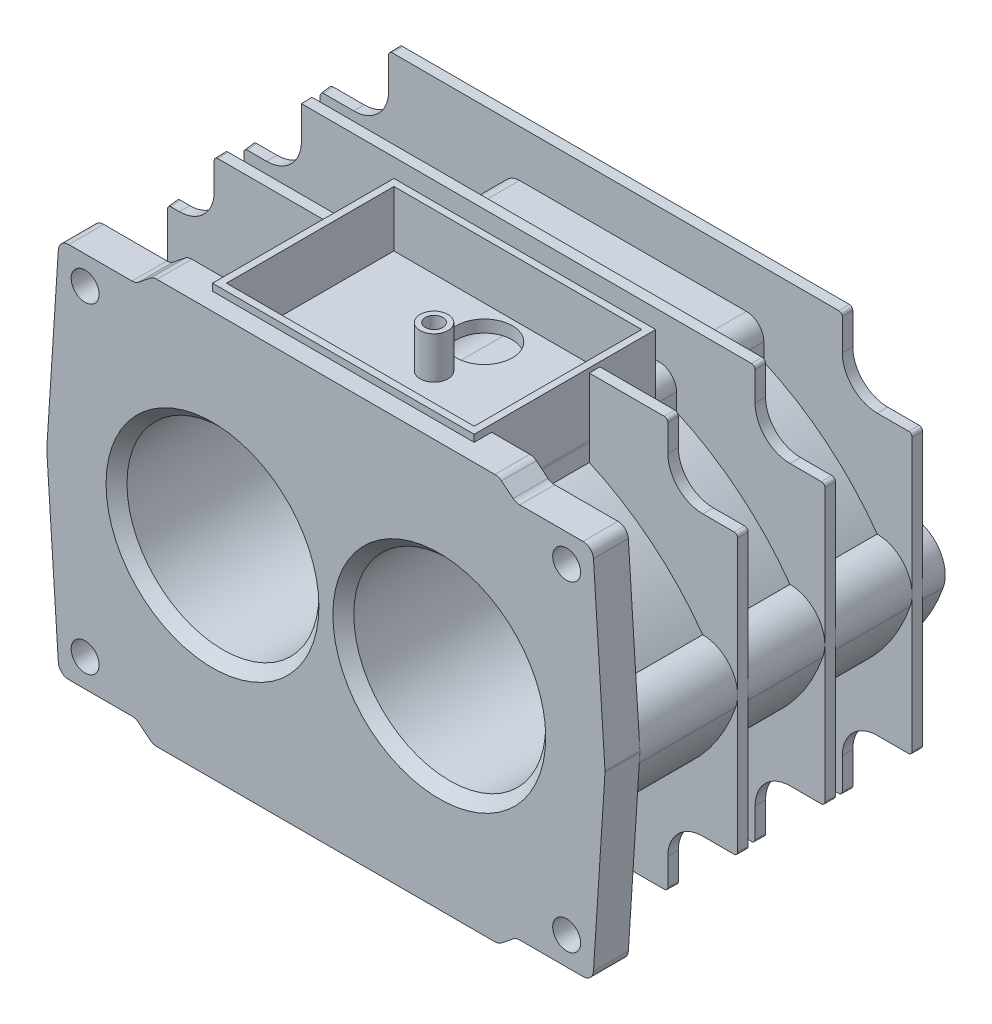
SolidWorks part; units mm, degrees
material "Ghisa grigia"
ref_plane "Piano frontale" through (0, 0, 0) normal (0, 0, 1) x (1, 0, 0)
ref_plane "Piano superiore" through (0, 0, 0) normal (0, 1, 0) x (1, 0, 0)
ref_plane "Piano destro" through (0, 0, 0) normal (1, 0, 0) x (0, 0, -1)
other "Centro di massa"
sketch "Schizzo1" plane through (0, 0, 0) normal (0, 0, 1) x (1, 0, 0)
  line L0 (-80, 0) -> (80, 0) construction
  line L1 (-76.5, 58) -> (76.5, 58) construction
  line L2 (-76.5, 58) -> (-76.5, -58) construction
  line L3 (-48.4477, -58) -> (48.4477, -58)
  line L4 (76.5, 58) -> (76.5, -58) construction
  line L5 (-76.5, 58) -> (76.5, -58) construction
  line L6 (-76.5, -58) -> (76.5, 58) construction
  line L7 (-76.5, -58) -> (76.5, -58) construction
  line L9 (79.9874, -0.194) -> (76.6819, -51.194)
  line L10 (76.6819, 51.194) -> (79.9874, 0.194)
  line L11 (48.4477, 58) -> (-48.4477, 58)
  line L12 (73.6881, -54) -> (55.5523, -54)
  line L13 (-69, 46) -> (69, 46) construction
  line L14 (-69, 46) -> (-69, -46) construction
  line L15 (-69, -46) -> (69, -46) construction
  line L16 (69, 46) -> (69, -46) construction
  line L17 (-69, 46) -> (69, -46) construction
  line L18 (-69, -46) -> (69, 46) construction
  line L19 (73.6881, 54) -> (55.5523, 54)
  line L20 (53.6783, 54.6574) -> (50.3217, 57.3426)
  line L21 (53.6783, -54.6574) -> (50.3217, -57.3426)
  line L22 (0, 72.4767) -> (0, -50.0988) construction
  line L23 (-53.6783, -54.6574) -> (-50.3217, -57.3426)
  line L24 (-73.6881, -54) -> (-55.5523, -54)
  line L25 (-79.9874, -0.194) -> (-76.6819, -51.194)
  line L26 (-76.6819, 51.194) -> (-79.9874, 0.194)
  line L27 (-73.6881, 54) -> (-55.5523, 54)
  line L28 (-53.6783, 54.6574) -> (-50.3217, 57.3426)
  circle A0 centre (-32.5, 0) radius 27.5
  circle A1 centre (32.5, 0) radius 27.5
  circle A2 centre (-69, 46) radius 4
  circle A3 centre (-69, -46) radius 4
  circle A4 centre (69, -46) radius 4
  circle A5 centre (69, 46) radius 4
  arc A6 (-79.9874, -0.194) -> (-79.9874, 0.194) centre (-76.9937, 0) cw
  arc A7 (-73.6881, -54) -> (-76.6819, -51.194) centre (-73.6881, -51) cw
  arc A8 (-53.6783, -54.6574) -> (-55.5523, -54) centre (-55.5523, -57) ccw
  arc A9 (-50.3217, -57.3426) -> (-48.4477, -58) centre (-48.4477, -55) ccw
  arc A10 (50.3217, -57.3426) -> (48.4477, -58) centre (48.4477, -55) cw
  arc A11 (53.6783, -54.6574) -> (55.5523, -54) centre (55.5523, -57) cw
  arc A12 (76.6819, -51.194) -> (73.6881, -54) centre (73.6881, -51) cw
  arc A13 (79.9874, 0.194) -> (79.9874, -0.194) centre (76.9937, 0) cw
  arc A14 (76.6819, 51.194) -> (73.6881, 54) centre (73.6881, 51) ccw
  arc A15 (53.6783, 54.6574) -> (55.5523, 54) centre (55.5523, 57) ccw
  arc A16 (50.3217, 57.3426) -> (48.4477, 58) centre (48.4477, 55) ccw
  arc A17 (-50.3217, 57.3426) -> (-48.4477, 58) centre (-48.4477, 55) cw
  arc A18 (-53.6783, 54.6574) -> (-55.5523, 54) centre (-55.5523, 57) cw
  arc A19 (-73.6881, 54) -> (-76.6819, 51.194) centre (-73.6881, 51) ccw
  point P0 (0, 0)
  point P8 (-32.5, 0)
  point P9 (32.5, 0)
  point P14 (0, 0)
  point P42 (-76.5, -54)
  point P45 (-54.5, -54)
  point P48 (-49.5, -58)
  point P51 (49.5, -58)
  point P54 (54.5, -54)
  point P57 (76.5, -54)
  point P63 (76.5, 54)
  point P66 (54.5, 54)
  point P69 (49.5, 58)
  point P72 (-49.5, 58)
  point P75 (-54.5, 54)
  point P78 (-76.5, 54)
  dimension "D5" = 55
  dimension "D6" = 55
  dimension "D11" = 8
  dimension "D12" = 8
  dimension "D13" = 8
  dimension "D14" = 8
  dimension "D7" = 3
  dimension "D1" = 153
  dimension "D2" = 116
  dimension "D3" = 44
  dimension "D4" = 44
  dimension "D8" = 80
  dimension "D9" = 138
  dimension "D10" = 92
  dimension "D15" = 54
  dimension "D16" = 54
  dimension "D17" = 22
  dimension "D18" = 22
  dimension "D19" = 5
  dimension "D20" = 5
  dimension "D21" = 58
extrude "Estrusione-Estrusione1" add sketch "Schizzo1" against normal blind 10
ref_plane "Piano1" through (0, 0, -97.5) normal (0, 0, 1) x (1, 0, 0)
sketch "Schizzo3" plane through (0, 0, -97.5) normal (0, 0, 1) x (1, 0, 0)
  line L0 (0, 73.6423) -> (0, -87.1965) construction
  line L1 (84.6322, 0) -> (-112.0106, 0) construction
  line L2 (37.5, -36.5) -> (37.5, -41.5)
  line L3 (32.5, 46.5) -> (-32.5, 46.5)
  line L4 (37.5, 41.5) -> (37.5, 36.5)
  line L5 (32.5, -46.5) -> (-32.5, -46.5)
  line L6 (-37.5, -36.5) -> (-37.5, -41.5)
  line L7 (37.5, 46.5) -> (0, 0) construction
  line L8 (37.5, -46.5) -> (0, 0) construction
  line L9 (-37.5, 41.5) -> (-37.5, 36.5)
  arc A0 (70, 10) -> (37.5, 36.5) centre (4.9622, -36.5841) ccw
  arc A1 (37.5, -36.5) -> (79.4378, -3.3059) centre (32.249, 13.2235) ccw
  arc A2 (79.4378, -3.3059) -> (70, 10) centre (70, 0) ccw
  arc A3 (-70, 10) -> (-79.4378, -3.3059) centre (-70, 0) ccw
  arc A4 (37.5, -41.5) -> (32.5, -46.5) centre (32.5, -41.5) cw
  arc A5 (32.5, 46.5) -> (37.5, 41.5) centre (32.5, 41.5) cw
  arc A6 (-37.5, -41.5) -> (-32.5, -46.5) centre (-32.5, -41.5) ccw
  arc A7 (-37.5, -36.5) -> (-79.4378, -3.3059) centre (-32.249, 13.2235) cw
  arc A8 (-79.4378, -3.3059) -> (-70, 10) centre (-70, 0) cw
  arc A9 (-70, 10) -> (-37.5, 36.5) centre (-4.9622, -36.5841) cw
  arc A10 (-32.5, 46.5) -> (-37.5, 41.5) centre (-32.5, 41.5) ccw
  point P5 (0, 0)
  point P6 (37.5, 36.5)
  point P10 (70, 0)
  point P18 (37.5, -36.5)
  point P28 (0, 46.5)
  point P29 (0, -46.5)
  point P33 (0, -46.5)
  point P44 (0, 46.5)
  dimension "D5" = 46.5
  dimension "D6" = 5
  dimension "D7" = 20
  dimension "D10" = 80
  dimension "D12" = 50
  dimension "D1" = 37.5
  dimension "D2" = 46.5
  dimension "D3" = 70
  dimension "D9" = 10
  dimension "D11" = 10
extrude "Estrusione-Estrusione2" add sketch "Schizzo3" along normal up to surface (87.5 mm away) contours L3 A10 L9 A9 A3 A7 L6 A6 L5 A4 L2 A1 A2 A0 L4 A5 region at (0, -0.827, -97.5) up to face at (73, 46, -10)
sketch "Schizzo5" plane through (0, 0, 0) normal (0, 0, 1) x (1, 0, 0)
  circle A0 centre (-32.5, 0) radius 27.5
  circle A1 centre (32.5, 0) radius 27.5
  circle A2 centre (32.5, 0) radius 27.5 construction
  dimension "D1" = 55
  dimension "D2" = 55
sketch "Schizzo6" plane through (0, 0, -97.5) normal (0, 0, -1) x (-1, 0, 0)
  line L0 (0, -56.2563) -> (0, 69.3145) construction
  line L1 (88.9615, 0) -> (-84.1365, 0) construction
  line L3 (-28.5, -37.5) -> (28.5, -37.5) construction
  line L4 (-28.5, -37.5) -> (-28.5, 37.5) construction
  line L5 (-28.5, 37.5) -> (28.5, 37.5) construction
  line L6 (28.5, -37.5) -> (28.5, 37.5) construction
  line L7 (-28.5, -37.5) -> (28.5, 37.5) construction
  line L8 (-28.5, 37.5) -> (28.5, -37.5) construction
  point P6 (-70, 0)
  point P7 (70, 0)
  point P8 (0, 0)
  dimension "D1" = 75
  dimension "D2" = 57
chamfer "Smusso1" distance 3 angle 45 2 edges at (-5, 0, 0) (60, 0, 0)
ref_plane "Piano3" through (0, 0, -91) normal (0, 0, 1) x (1, 0, 0)
sketch "Schizzo14" plane through (0, 0, -91) normal (0, 0, 1) x (1, 0, 0)
  line L0 (80, -60) -> (80, 60)
  line L1 (-21.8426, 0) -> (80, 0) construction
  line L2 (80, 60) -> (-90, 60)
  line L3 (80, -60) -> (-90, -60)
  line L4 (-90, 60) -> (-90, -60)
  line L6 (32.5, 46.5) -> (-32.5, 46.5)
  line L7 (37.5, 36.5) -> (37.5, 41.5)
  line L8 (37.5, -41.5) -> (37.5, -36.5)
  line L9 (-32.5, -46.5) -> (32.5, -46.5)
  line L10 (-37.5, -36.5) -> (-37.5, -41.5)
  line L11 (-37.5, 41.5) -> (-37.5, 36.5)
  line L12 (32.5, 46.5) -> (-32.5, 46.5)
  line L13 (37.5, 36.5) -> (37.5, 41.5)
  line L14 (37.5, -41.5) -> (37.5, -36.5)
  line L15 (-32.5, -46.5) -> (32.5, -46.5)
  line L16 (-37.5, -36.5) -> (-37.5, -41.5)
  line L17 (-37.5, 41.5) -> (-37.5, 36.5)
  arc A10 (37.5, 41.5) -> (32.5, 46.5) centre (32.5, 41.5) ccw
  arc A11 (70, 10) -> (37.5, 36.5) centre (4.9622, -36.5841) ccw
  arc A12 (79.4378, -3.3059) -> (70, 10) centre (70, 0) ccw
  arc A13 (37.5, -36.5) -> (79.4378, -3.3059) centre (32.249, 13.2235) ccw
  arc A14 (32.5, -46.5) -> (37.5, -41.5) centre (32.5, -41.5) ccw
  arc A15 (-37.5, -41.5) -> (-32.5, -46.5) centre (-32.5, -41.5) ccw
  arc A16 (-79.4378, -3.3059) -> (-37.5, -36.5) centre (-32.249, 13.2235) ccw
  arc A17 (-70, 10) -> (-79.4378, -3.3059) centre (-70, 0) ccw
  arc A18 (-37.5, 36.5) -> (-70, 10) centre (-4.9622, -36.5841) ccw
  arc A19 (-32.5, 46.5) -> (-37.5, 41.5) centre (-32.5, 41.5) ccw
  arc A20 (37.5, 41.5) -> (32.5, 46.5) centre (32.5, 41.5) ccw
  arc A21 (70, 10) -> (37.5, 36.5) centre (4.9622, -36.5841) ccw
  arc A22 (79.4378, -3.3059) -> (70, 10) centre (70, 0) ccw
  arc A23 (37.5, -36.5) -> (79.4378, -3.3059) centre (32.249, 13.2235) ccw
  arc A24 (32.5, -46.5) -> (37.5, -41.5) centre (32.5, -41.5) ccw
  arc A25 (-37.5, -41.5) -> (-32.5, -46.5) centre (-32.5, -41.5) ccw
  arc A26 (-79.4378, -3.3059) -> (-37.5, -36.5) centre (-32.249, 13.2235) ccw
  arc A27 (-70, 10) -> (-79.4378, -3.3059) centre (-70, 0) ccw
  arc A28 (-37.5, 36.5) -> (-70, 10) centre (-4.9622, -36.5841) ccw
  arc A29 (-32.5, 46.5) -> (-37.5, 41.5) centre (-32.5, 41.5) ccw
  point P9 (0, 0)
  dimension "D2" = 60
  dimension "D3" = 60
  dimension "D4" = 170
  dimension "D5" = 170
  dimension "D1" = 0
extrude "Estrusione-Estrusione11" add sketch "Schizzo14" along normal blind 3 contours L2 L4 L3 L0
ref_axis "Assi1" through (0, 0, 4.5) along (0, 0, -1)
pattern_linear "Ripetizione a L1" count 3 spacing 25 along (0, 0, 1) of "Estrusione-Estrusione11"
sketch "Schizzo15" plane through (0, 0, -91) normal (0, 0, -1) x (-1, 0, 0)
  line L0 (127.0533, 0) -> (-116.8058, 0) construction
  line L1 (0, 52.5478) -> (0, -56.6592) construction
  line L2 (-70, -40) -> (-80, -40)
  line L3 (-80, -60) -> (-80, 0) construction
  line L4 (-60, -50) -> (-60, -60)
  line L5 (-80, -60) -> (90, -60) construction
  line L6 (-80, -40) -> (-80, -60)
  line L7 (-60, -60) -> (-80, -60)
  line L8 (-60, 60) -> (-80, 60)
  line L9 (-80, 40) -> (-80, 60)
  line L10 (-70, 40) -> (-80, 40)
  line L11 (-60, 50) -> (-60, 60)
  line L12 (90, -40) -> (80, -40)
  line L15 (90, 60) -> (90, -60) construction
  line L16 (70, -50) -> (70, -60)
  line L17 (90, -40) -> (90, -60)
  line L18 (70, -60) -> (90, -60)
  line L19 (70, 60) -> (90, 60)
  line L20 (90, 40) -> (90, 60)
  line L21 (90, 40) -> (80, 40)
  line L22 (70, 50) -> (70, 60)
  arc A0 (-60, -50) -> (-70, -40) centre (-70, -50) ccw
  arc A1 (-60, 50) -> (-70, 40) centre (-70, 50) cw
  arc A3 (80, -40) -> (70, -50) centre (80, -50) ccw
  arc A4 (80, 40) -> (70, 50) centre (80, 50) cw
  dimension "D3" = 10
  dimension "D6" = 10
  dimension "D1" = 40
  dimension "D2" = 60
  dimension "D4" = 70
  dimension "D5" = 40
extrude "Taglio-Estrusione2" cut sketch "Schizzo15" against normal blind 62
hole_wizard "Foro filettato M8-1" positions "Schizzo3D1" profile "Schizzo7" tap size "M8" standard "DIN"
sketch3d "Schizzo3D1"
  point P0 (-28.5, -37.5, -97.5)
  point P3 (-28.5, 37.5, -97.5)
  point P6 (28.5, 37.5, -97.5)
  point P9 (28.5, -37.5, -97.5)
  point P12 (70, 0, -97.5)
  point P15 (-70, 0, -97.5)
sketch "Schizzo7" plane through (-28.5, -37.5, -97.5) normal (1, 0, 0) x (0, 1, 0)
  line L0 (0, 0) -> (0, 37.0429)
  line L1 (0, 37.0429) -> (3.4, 35)
  line L2 (3.4, 35) -> (3.4, 0)
  line L5 (3.4, 0) -> (0, 0)
  line L10 (0, 37.0429) -> (-3.4, 35) construction
  line L11 (0, -6.35) -> (0, 107.95) construction
  dimension "Tap Drill Dia." = 6.8
  dimension "Tap Drill Depth" = 35
  dimension "Drill Angle" = 118
cosmetic thread "Filettatura del foro1" parameters "D1"=30, "D2"=8
cosmetic thread "Filettatura del foro2" parameters "D1"=30, "D2"=8
cosmetic thread "Filettatura del foro3" parameters "D1"=30, "D2"=8
cosmetic thread "Filettatura del foro4" parameters "D1"=30, "D2"=8
cosmetic thread "Filettatura del foro5" parameters "D1"=30, "D2"=8
cosmetic thread "Filettatura del foro6" parameters "D1"=30, "D2"=8
extrude "Taglio-Estrusione3" cut sketch "Schizzo5" against normal blind 197
sketch "Schizzo16" plane through (0, 0, 0) normal (0, 1, 0) x (1, 0, 0)
  line L0 (-90, 91) -> (-79.9163, 10)
  arc A0 (-90, 91) -> (-79.9163, 10) centre (-52.2516, 54.5716) ccw
extrude "Taglio-Estrusione4" cut sketch "Schizzo16" against normal blind 197 and the other way blind 197
sketch "Schizzo17" plane through (0, 0, 0) normal (1, 0, 0) x (0, 0, -1)
  line L0 (91, 60) -> (10, 58)
  line L1 (-33.0559, 0) -> (91.2748, 0) construction
  line L2 (91, -60) -> (10, -58)
  arc A0 (91, 60) -> (10, 58) centre (51.3044, 26.4235) ccw
  arc A1 (91, -60) -> (10, -58) centre (51.3044, -26.4235) cw
  dimension "D1" = 51.9916
extrude "Taglio-Estrusione5" cut sketch "Schizzo17" against normal blind 197 and the other way blind 197
ref_plane "Piano6" through (0, 60, 0) normal (0, 1, 0) x (1, 0, 0)
sketch "Schizzo18" plane through (0, 60, 0) normal (0, 1, 0) x (1, 0, 0)
  line L0 (0, -13.7764) -> (0, 107.1295) construction
  line L2 (-37.5, 57) -> (37.5, 57)
  line L3 (-37.5, 57) -> (-37.5, 5)
  line L4 (-37.5, 5) -> (37.5, 5)
  line L5 (37.5, 57) -> (37.5, 5)
  line L6 (48.4477, 0) -> (-48.4477, 0) construction
  dimension "D1" = 37.5
  dimension "D2" = 37.5
  dimension "D3" = 5
  dimension "D4" = 52
extrude "Estrusione-Estrusione12" add sketch "Schizzo18" against normal blind 18
sketch "Schizzo19" plane through (0, 60, 0) normal (0, 1, 0) x (1, 0, 0)
  line L8 (-35.5, 55) -> (-35.5, 7)
  line L9 (-35.5, 7) -> (35.5, 7)
  line L10 (35.5, 7) -> (35.5, 55)
  line L11 (35.5, 55) -> (-35.5, 55)
  line L12 (-35.5, 55) -> (-35.5, 7)
  line L13 (-35.5, 7) -> (35.5, 7)
  line L14 (35.5, 7) -> (35.5, 55)
  line L15 (35.5, 55) -> (-35.5, 55)
  dimension "D1" = 2
extrude "Taglio-Estrusione6" cut sketch "Schizzo19" against normal blind 16
ref_plane "Piano7" through (0, 0, -78.5) normal (0, 0, 1) x (1, 0, 0)
sketch "Schizzo20" plane through (0, 0, -78.5) normal (0, 0, 1) x (1, 0, 0)
  line L0 (0, 25.5551) -> (0, -54.7974) construction
  line L1 (30, -46.5) -> (-30, -46.5)
  line L2 (25, -54.5) -> (-25, -54.5)
  line L3 (30, -46.5) -> (30, -49.5)
  line L4 (-30, -46.5) -> (-30, -49.5)
  arc A0 (-25, -54.5) -> (-30, -49.5) centre (-25, -49.5) cw
  arc A1 (25, -54.5) -> (30, -49.5) centre (25, -49.5) ccw
  point P2 (0, 0)
  dimension "D5" = 5
  dimension "D1" = 46.5
  dimension "D2" = 30
  dimension "D3" = 30
  dimension "D4" = 8
extrude "Estrusione-Estrusione13" add sketch "Schizzo20" along normal blind 3
pattern_linear "Ripetizione a L2" count 3 spacing 25 along (0, 0, 1) of "Estrusione-Estrusione13"
ref_plane "Piano8" through (0, -60, 0) normal (0, 1, 0) x (1, 0, 0)
sketch "Schizzo21" plane through (0, -60, 0) normal (0, 1, 0) x (1, 0, 0)
  line L0 (0, -7.3364) -> (0, 97.9361) construction
  line L1 (11.1924, 0) -> (-27.1627, 0) construction
  circle A0 centre (0, 24.5) radius 14
  dimension "D1" = 28
  dimension "D2" = 24.5
extrude "Estrusione-Estrusione17" add sketch "Schizzo21" along normal up to surface (13.5 mm away) contours A0 up to face at (0, -46.5, -27)
sketch "Schizzo22" plane through (0, 0, -97.5) normal (0, 0, -1) x (-1, 0, 0)
  line L0 (0, 65.5521) -> (0, -71.7501) construction
  line L1 (-32.5, 46.5) -> (32.5, 46.5) construction
  line L2 (-14.2573, 40.5) -> (14.2573, 40.5)
  line L3 (-20, 34.7573) -> (-20, 34.2427)
  line L4 (-14.2573, 28.5) -> (14.2573, 28.5)
  line L5 (20, 34.7573) -> (20, 34.2427)
  line L6 (-15, -40.5) -> (15, -40.5)
  line L7 (-32.5, -46.5) -> (32.5, -46.5) construction
  line L8 (-20, -35.5) -> (-20, -34.2929)
  line L9 (20, -35.5) -> (20, -34.2929)
  line L10 (1.0675, -14.5) -> (-1.0675, -14.5)
  arc A0 (20, 34.7573) -> (14.2573, 40.5) centre (14.2573, 34.7573) ccw
  arc A1 (14.2573, 28.5) -> (20, 34.2427) centre (14.2573, 34.2427) ccw
  arc A2 (-20, 34.2427) -> (-14.2573, 28.5) centre (-14.2573, 34.2427) ccw
  arc A3 (-20, 34.7573) -> (-14.2573, 40.5) centre (-14.2573, 34.7573) cw
  arc A4 (-17.2727, -29.8392) -> (-2.8384, -15.5704) centre (-32.5, 0) ccw
  arc A5 (2.8384, -15.5704) -> (17.2727, -29.8392) centre (32.5, 0) ccw
  arc A6 (-20, -34.2929) -> (-17.2727, -29.8392) centre (-15, -34.2929) cw
  arc A7 (20, -34.2929) -> (17.2727, -29.8392) centre (15, -34.2929) ccw
  arc A8 (15, -40.5) -> (20, -35.5) centre (15, -35.5) ccw
  arc A9 (-20, -35.5) -> (-15, -40.5) centre (-15, -35.5) ccw
  arc A10 (1.0675, -14.5) -> (2.8384, -15.5704) centre (1.0675, -16.5) cw
  arc A11 (-1.0675, -14.5) -> (-2.8384, -15.5704) centre (-1.0675, -16.5) ccw
  point P16 (-20, 28.5)
  point P19 (-20, 40.5)
  point P38 (20, -40.5)
  point P41 (-20, -40.5)
  dimension "D5" = 5.7427
  dimension "D9" = 67
  dimension "D10" = 67
  dimension "D12" = 5
  dimension "D13" = 2
  dimension "D1" = 20
  dimension "D2" = 20
  dimension "D3" = 6
  dimension "D4" = 12
  dimension "D6" = 6
  dimension "D7" = 20
  dimension "D8" = 20
  dimension "D11" = 26
extrude "Taglio-Estrusione7" cut sketch "Schizzo22" against normal blind 75
sketch "Schizzo23" plane through (0, -60, 0) normal (0, -1, 0) x (1, 0, 0)
  circle A0 centre (0, -24.5) radius 9.6466
  circle A1 centre (0, -24.5) radius 14 construction
  dimension "D1" = 19.2932
hole_wizard "Foro filettato M24-1" positions "Schizzo3D3" profile "Schizzo25" tap size "M24" standard "DIN"
sketch3d "Schizzo3D3"
  point P0 (0, -60, -24.5)
sketch "Schizzo25" plane through (0, -60, -24.5) normal (1, 0, 0) x (0, 0, -1)
  line L0 (0, 0) -> (0, 31.309)
  line L1 (0, 31.309) -> (10.5, 25)
  line L2 (10.5, 25) -> (10.5, 0)
  line L5 (10.5, 0) -> (0, 0)
  line L10 (0, 31.309) -> (-10.5, 25) construction
  line L11 (0, -6.35) -> (0, 107.95) construction
  dimension "Tap Drill Dia." = 21
  dimension "Tap Drill Depth" = 25
  dimension "Drill Angle" = 118
cosmetic thread "Filettatura del foro7" parameters "D1"=25, "D2"=24
sketch "Schizzo26" plane through (0, 44, 0) normal (0, 1, 0) x (1, 0, 0)
  line L0 (-35.5, 7) -> (35.5, 7) construction
  line L2 (-35.5, 55) -> (-35.5, 7) construction
  circle A0 centre (0, 31) radius 4
  dimension "D1" = 8
  dimension "D2" = 24
  dimension "D3" = 35.5
extrude "Estrusione-Estrusione18" add sketch "Schizzo26" along normal blind 12
hole_wizard "Foro filettato M6-1" positions "Schizzo3D4" profile "Schizzo27" tap size "M6" standard "DIN"
sketch3d "Schizzo3D4"
  line L0 (0, 56, -31) -> (0, 44, -31) construction
  point P0 (0, 56, -31)
sketch "Schizzo27" plane through (0, 56, -31) normal (1, 0, 0) x (0, 0, 1)
  line L0 (0, 0) -> (0, 13.5022)
  line L1 (0, 13.5022) -> (2.5, 12)
  line L2 (2.5, 12) -> (2.5, 0)
  line L5 (2.5, 0) -> (0, 0)
  line L10 (0, 13.5022) -> (-2.5, 12) construction
  line L11 (0, -6.35) -> (0, 107.95) construction
  dimension "Tap Drill Dia." = 5
  dimension "Tap Drill Depth" = 12
  dimension "Drill Angle" = 118
cosmetic thread "Filettatura del foro8" parameters "D1"=12, "D2"=6
sketch "Schizzo28" plane through (0, 44, 0) normal (0, 1, 0) x (1, 0, 0)
  line L0 (35.5, 7) -> (35.5, 55) construction
  line L1 (-35.5, 7) -> (35.5, 7) construction
  circle A0 centre (0, 45.4088) radius 8
  dimension "D1" = 16
  dimension "D2" = 35.5
  dimension "D3" = 38.4088
extrude "Taglio-Estrusione8" cut sketch "Schizzo28" against normal blind 12
fillet "Raccordo11" radius 1 23 edges at (-70, 59.963, -89.5) (-89.8133, 40, -89.5) (-86.701, 40, -64.5) (-70, 58.7284, -39.5) (-83.5888, 40, -39.5) (80, 40, -89.5) (60, 59.963, -89.5) (60, 59.3457, -64.5) (80, 40, -64.5) (80, 40, -39.5) (60, 58.7284, -39.5) (80, -40, -39.5) (60, -58.7284, -39.5) (60, -59.3457, -64.5) (80, -40, -64.5) (80, -40, -89.5) (60, -59.963, -89.5) (-70, -58.7284, -39.5) (-83.5888, -40, -39.5) (-70, -59.3457, -64.5) (-86.701, -40, -64.5) (-89.8133, -40, -89.5) (-70, -59.963, -89.5)
fillet "Raccordo14" radius 2 6 edges at (37.5, -36.5, -94.25) (-37.5, -36.5, -94.25) (-70, 10, -94.25) (-37.5, 36.5, -94.25) (37.5, 36.5, -94.25) (70, 10, -94.25)
fillet "Raccordo15" radius 2 17 edges at (30, -46.5, -77) (30, -46.5, -27) (9.7916, -46.5, -34.5063) (21.7082, -46.5, -28.5) (-9.7916, -46.5, -34.5063) (-21.7082, -46.5, -28.5) (-30, -46.5, -27) (21.9821, -46.5, -25.5) (0, -46.5, -10.5) (-21.9821, -46.5, -25.5) (0, -46.5, -50.5) (0, -46.5, -75.5) (30, -46.5, -52) (-30, -46.5, -52) (0, -46.5, -53.5) (-30, -46.5, -77) (0, -46.5, -78.5)
